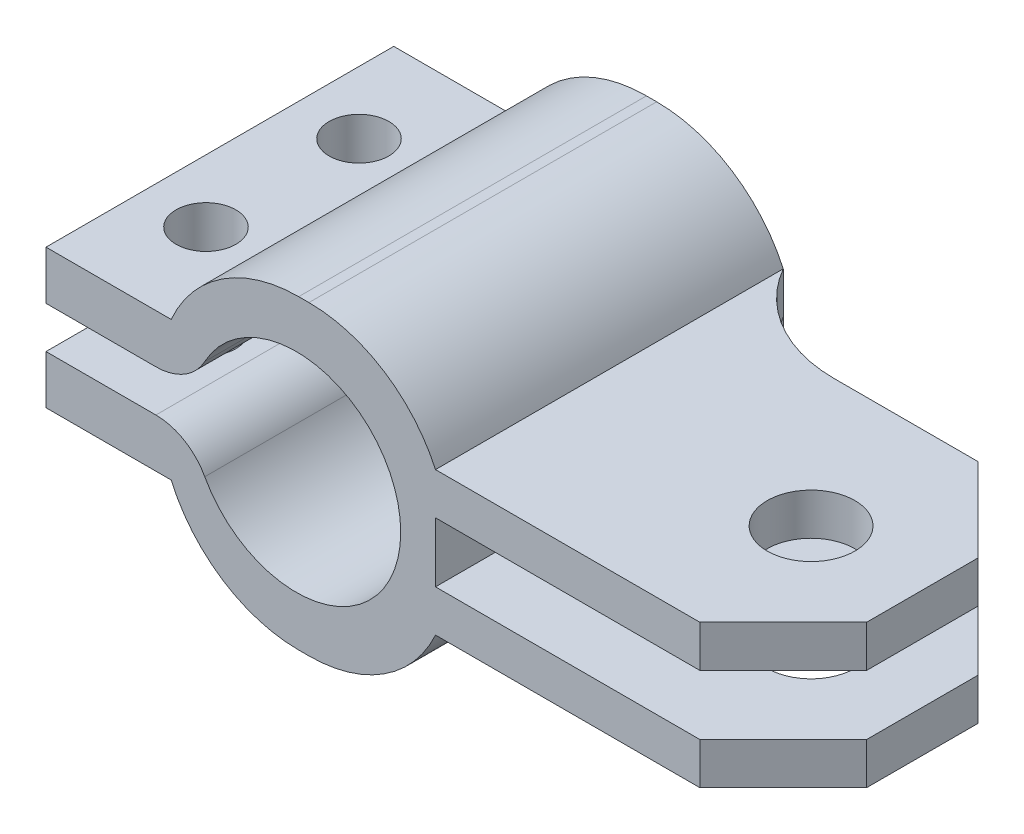
SolidWorks part; units mm, degrees
ref_plane "前视基准面" through (0, 0, 0) normal (0, 0, 1) x (1, 0, 0)
ref_plane "上视基准面" through (0, 0, 0) normal (0, 1, 0) x (1, 0, 0)
ref_plane "右视基准面" through (0, 0, 0) normal (1, 0, 0) x (0, 0, -1)
sketch "草图1" plane through (0, 0, 0) normal (0, 0, 1) x (1, 0, 0)
  line L1 (12.5, -11) -> (-12.5, -11)
  line L2 (12.5, -11) -> (12.5, 11)
  line L3 (12.5, 11) -> (-12.5, 11)
  line L4 (-12.5, -11) -> (-12.5, 11)
  line L5 (12.5, -11) -> (-12.5, 11) construction
  line L6 (12.5, 11) -> (-12.5, -11) construction
  circle A0 centre (2.5, 0) radius 7.5
  point P0 (0, 0)
  dimension "D3" = 15
  dimension "D4" = 15
  dimension "D5" = 11
  dimension "D1" = 22
  dimension "D2" = 25
extrude "凸台-拉伸1" add sketch "草图1" along normal blind 25
sketch "草图2" plane through (12.5, 0, 0) normal (1, 0, 0) x (0, 0, -1)
  line L0 (-25, -11) -> (-25, 11) construction
  line L1 (-25, 5.15) -> (-5, 5.15)
  line L2 (-25, 5.15) -> (-25, 2.15)
  line L3 (-25, 2.15) -> (-5, 2.15)
  line L4 (-5, 5.15) -> (-5, 2.15)
  line L6 (-25, -2.15) -> (-5, -2.15)
  line L7 (-25, -2.15) -> (-25, -5.15)
  line L8 (-25, -5.15) -> (-5, -5.15)
  line L9 (-5, -2.15) -> (-5, -5.15)
  dimension "D1" = 20
  dimension "D2" = 20
  dimension "D3" = 4.3
  dimension "D4" = 3
  dimension "D5" = 3
  dimension "D6" = 2.15
extrude "凸台-拉伸2" add sketch "草图2" along normal blind 25
sketch "草图3" plane through (0, 5.15, 0) normal (0, 1, 0) x (1, 0, 0)
  line L0 (37.5, -5) -> (37.5, -25) construction
  line L1 (37.5, -5) -> (12.5, -5) construction
  circle A0 centre (29.5, -15) radius 3.15
  dimension "D1" = 6.3
  dimension "D2" = 8
  dimension "D3" = 10
extrude "切除-拉伸1" cut sketch "草图3" against normal blind 25
fillet "圆角1" [suppressed] radius 10
fillet "圆角2" radius 10 2 edges at (12.5, -3.65, 5) (12.5, 3.65, 5)
sketch "草图4" plane through (0, 0, 0) normal (0, 0, -1) x (-1, 0, 0)
  line L1 (12.5, 11) -> (6.5, 11)
  line L2 (12.5, 11) -> (12.5, 5)
  line L3 (12.5, 5) -> (6.5, 5)
  line L4 (6.5, 11) -> (6.5, 5)
  line L5 (12.5, -11) -> (6.5, -11)
  line L6 (12.5, -11) -> (12.5, -5)
  line L7 (12.5, -5) -> (6.5, -5)
  line L8 (6.5, -11) -> (6.5, -5)
  dimension "D1" = 6
  dimension "D2" = 6
  dimension "D3" = 6
  dimension "D4" = 6
extrude "切除-拉伸2" cut sketch "草图4" against normal blind 25
fillet "圆角3" radius 10 2 edges at (-6.5, -11, 12.5) (-6.5, 11, 12.5)
fillet "圆角4" radius 10 2 edges at (12.5, 11, 12.5) (12.5, -11, 12.5)
sketch "草图5" plane through (0, 0, 0) normal (0, 0, -1) x (-1, 0, 0)
  line L0 (12.5, 5) -> (12.5, -5) construction
  line L1 (23.358, 1.5) -> (1.642, 1.5)
  line L2 (23.358, 1.5) -> (23.358, -1.5)
  line L3 (23.358, -1.5) -> (1.642, -1.5)
  line L4 (1.642, 1.5) -> (1.642, -1.5)
  line L5 (23.358, 1.5) -> (1.642, -1.5) construction
  line L6 (23.358, -1.5) -> (1.642, 1.5) construction
  point P0 (12.5, 0)
  dimension "D1" = 3
extrude "切除-拉伸3" cut sketch "草图5" against normal blind 25
fillet "圆角5" radius 4 2 edges at (-4.8485, -1.5, 12.5) (-4.8485, 1.5, 12.5)
sketch "草图8" plane through (-12.5, 0, 0) normal (-1, 0, 0) x (0, 0, 1)
  line L4 (0, 5) -> (0, 1.5)
  line L5 (0, 1.5) -> (25, 1.5)
  line L6 (25, 1.5) -> (25, 5)
  line L8 (0, 5) -> (0, 1.5)
  line L9 (0, 1.5) -> (25, 1.5)
  line L12 (25, -5) -> (25, -1.5)
  line L14 (0, -1.5) -> (0, -5)
  line L15 (0, -5) -> (25, -5)
  line L18 (0, -1.5) -> (0, -5)
  line L19 (0, -5) -> (25, -5)
  line L20 (25, 1.5) -> (25, 5)
  line L22 (25, -5) -> (25, -1.5)
  line L24 (25, 5) -> (0, 5)
  line L25 (25, 5) -> (0, 5)
  line L26 (25, -1.5) -> (0, -1.5)
  line L27 (25, -1.5) -> (0, -1.5)
  dimension "D1" = 0
  dimension "D2" = 0
extrude "凸台-拉伸3" add sketch "草图8" along normal blind 3
sketch "草图6" plane through (0, 5, 0) normal (0, 1, 0) x (1, 0, 0)
  line L0 (-6.5, 0) -> (-15.5, 0) construction
  line L1 (-6.5, -25) -> (-15.5, -25) construction
  line L3 (-6.5, -25) -> (-6.5, 0) construction
  circle A0 centre (-11, -7) radius 2.15
  circle A1 centre (-11, -18) radius 2.15
  dimension "D1" = 4.3
  dimension "D2" = 4.3
  dimension "D3" = 7
  dimension "D4" = 7
  dimension "D5" = 4.5
  dimension "D6" = 4.5
extrude "切除-拉伸4" cut sketch "草图6" against normal blind 25
chamfer "倒角1" distance 6 angle 45 4 edges at (37.5, 3.65, 5) (37.5, -3.65, 5) (37.5, 3.65, 25) (37.5, -3.65, 25)
